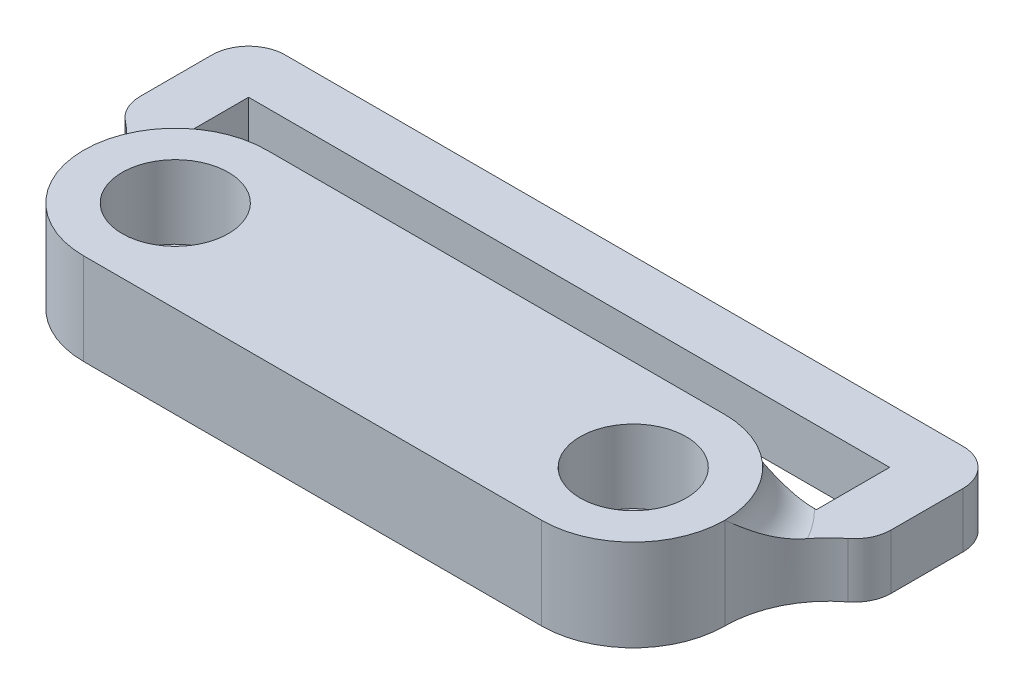
SolidWorks part; units mm, degrees
ref_plane "前视基准面" through (0, 0, 0) normal (0, 0, 1) x (1, 0, 0)
ref_plane "上视基准面" through (0, 0, 0) normal (0, 1, 0) x (1, 0, 0)
ref_plane "右视基准面" through (0, 0, 0) normal (1, 0, 0) x (0, 0, -1)
sketch "草图1" plane through (0, 0, 0) normal (0, 1, 0) x (1, 0, 0)
  line L0 (-12.5, 0) -> (12.5, 0) construction
  line L1 (-12.5, 5) -> (12.5, 5)
  line L2 (-12.5, -5) -> (12.5, -5)
  arc A0 (-12.5, 5) -> (-12.5, -5) centre (-12.5, 0) ccw
  arc A1 (12.5, -5) -> (12.5, 5) centre (12.5, 0) ccw
  circle A2 centre (12.5, 0) radius 1.6
  circle A3 centre (-12.5, 0) radius 1.6
  point P2 (0, 0)
  dimension "D2" = 3.2
  dimension "D3" = 5
  dimension "D1" = 25
extrude "凸台-拉伸1" add sketch "草图1" along normal blind 5
sketch "草图2" plane through (0, 5, 0) normal (0, 1, 0) x (1, 0, 0)
  circle A0 centre (-12.5, 0) radius 2.9
  circle A1 centre (12.5, 0) radius 2.9
  dimension "D1" = 5.8
extrude "切除-拉伸1" cut sketch "草图2" against normal blind 4
sketch "草图3" plane through (0, 0, 0) normal (0, -1, 0) x (1, 0, 0)
  line L0 (0, 0) -> (0, -36.3054) construction
  line L1 (-20.5, -5) -> (-20.5, -12)
  line L2 (20.5, -5) -> (20.5, -12)
  line L3 (-20.5, -5) -> (20.5, -5)
  line L4 (-20.5, -12) -> (20.5, -12)
  line L5 (12.5, -5) -> (-12.5, -5) construction
  line L6 (-17.5, -5) -> (17.5, -5)
  line L7 (-17.5, -5) -> (-17.5, -9)
  line L8 (-17.5, -9) -> (17.5, -9)
  line L9 (17.5, -5) -> (17.5, -9)
  arc A0 (-20.5, -5) -> (-17.5, 0) centre (-23.1667, 0) ccw
  arc A1 (-12.5, 5) -> (-12.5, -5) centre (-12.5, 0) ccw construction
  arc A2 (-12.5, 5) -> (-12.5, -5) centre (-12.5, 0) ccw
  arc A3 (12.5, 5) -> (12.5, -5) centre (12.5, 0) cw
  arc A4 (20.5, -5) -> (17.5, 0) centre (23.1667, 0) cw
  point P16 (-17.274, -1.4864)
  point P25 (-17.5, 0)
  arc M2 (-12.5, 5) -> (-12.5, -5) centre (-12.5, 0) ccw
  line M3 (-12.5, -5) -> (12.5, -5)
  arc M4 (12.5, -5) -> (12.5, 5) centre (12.5, 0) ccw
  dimension "D5" = 10.6667
  dimension "D1" = 7
  dimension "D2" = 3
  dimension "D3" = 3
  dimension "D4" = 35
extrude "凸台-拉伸2" add sketch "草图3" against normal blind 3 contours L0 L8 L7 L1 L4 M3 | L8 L0 L4 L2 L9 M3 | A0 L3 M2 | L3 A4 M4
fillet "圆角1" radius 2 6 edges at (20.5, 1.5, -12) (-20.5, 1.5, -12) (-20.5, 1.5, -5) (20.5, 1.5, -5) (-16.0355, 3, -3.5355) (16.0355, 3, -3.5355)
